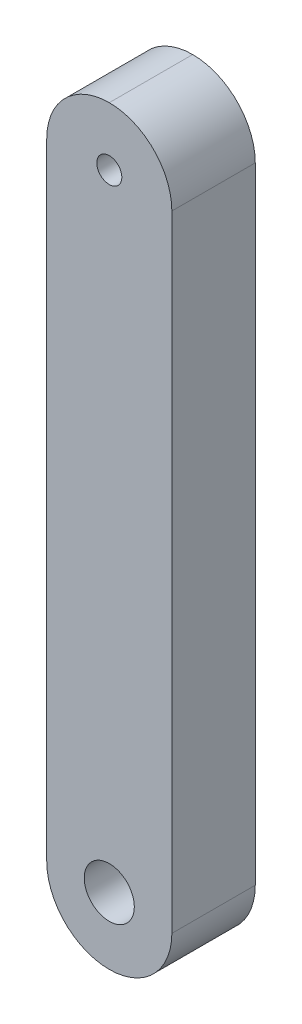
SolidWorks part; units mm, degrees
ref_plane "Front" through (0, 0, 0) normal (0, 0, 1) x (1, 0, 0)
ref_plane "Top" through (0, 0, 0) normal (0, 1, 0) x (1, 0, 0)
ref_plane "Right" through (0, 0, 0) normal (1, 0, 0) x (0, 0, -1)
sketch "Esquisse1" plane through (0, 0, 0) normal (0, 0, 1) x (1, 0, 0)
  line L1 (0, 0) -> (15, 0)
  line L2 (0, 0) -> (0, 90)
  line L3 (0, 90) -> (15, 90)
  line L4 (15, 0) -> (15, 90)
  dimension "D1" = 15
  dimension "D2" = 90
extrude "Boss.-Extru.1" add sketch "Esquisse1" along normal blind 10
sketch "Esquisse2" plane through (0, 0, 10) normal (0, 0, 1) x (1, 0, 0)
  line L0 (7.5, 83) -> (7.5, 90) construction
  line L1 (15, 90) -> (0, 90) construction
  line L2 (0, 0) -> (15, 0) construction
  line L3 (7.5, 8) -> (7.5, 0) construction
  circle A1 centre (7.5, 83) radius 1.5
  circle A2 centre (7.5, 8) radius 3
  point P11 (7.5, 0)
  dimension "D2" = 7
  dimension "D3" = 3
  dimension "D4" = 6
  dimension "D5" = 8
extrude "Enlèv. mat.-Extru.1" cut sketch "Esquisse2" against normal up to vertex (10 mm away) up to point (0, 90, 0)
fillet "Congé1" radius 7.5 4 edges at (15, 90, 5) (0, 90, 5) (15, 0, 5) (0, 0, 5)
